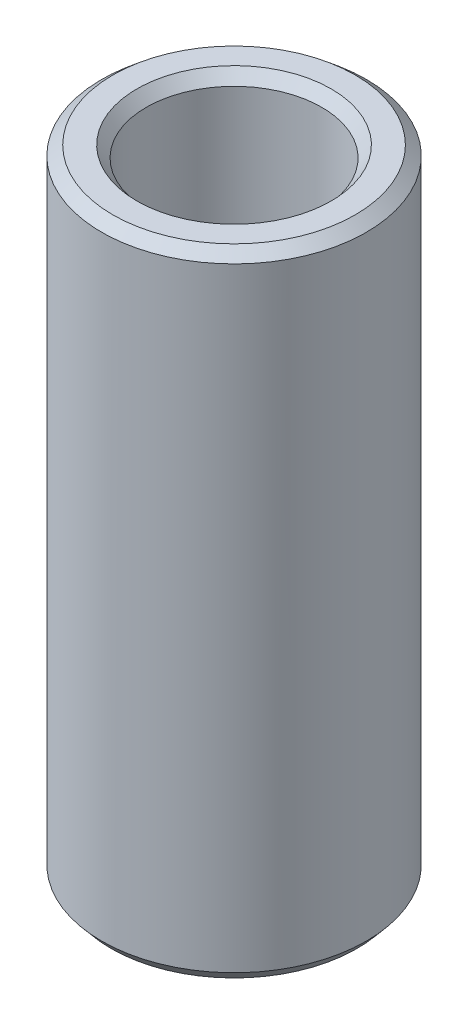
SolidWorks part; units mm, degrees
ref_plane "Front Plane" through (0, 0, 0) normal (0, 0, 1) x (1, 0, 0)
ref_plane "Top Plane" through (0, 0, 0) normal (0, 1, 0) x (1, 0, 0)
ref_plane "Right Plane" through (0, 0, 0) normal (1, 0, 0) x (0, 0, -1)
sketch "Sketch1" plane through (0, 0, 0) normal (0, 1, 0) x (1, 0, 0)
  circle A0 centre (0, 0) radius 50
  dimension "SLEEVE_OD" = 100
extrude "Boss-Extrude1" add sketch "Sketch1" along normal blind 239.631
sketch "Sketch2" plane through (0, 0, 0) normal (0, 1, 0) x (1, 0, 0)
  circle A0 centre (0, 0) radius 33.1311
  dimension "BORE_D" = 66.2622
extrude "Cut-Extrude1" cut sketch "Sketch2" along normal through all
chamfer "Chamfer1" distance 3.5622 angle 49.943 4 edges at (0, 239.631, 33.1311) (0, 0, 33.1311) (0, 0, 50) (0, 239.631, 50) first distance on face at (0, 239.631, 33.1311) first distance on face at (0, 0, 33.1311) first distance on face at (0, 239.631, 50)
